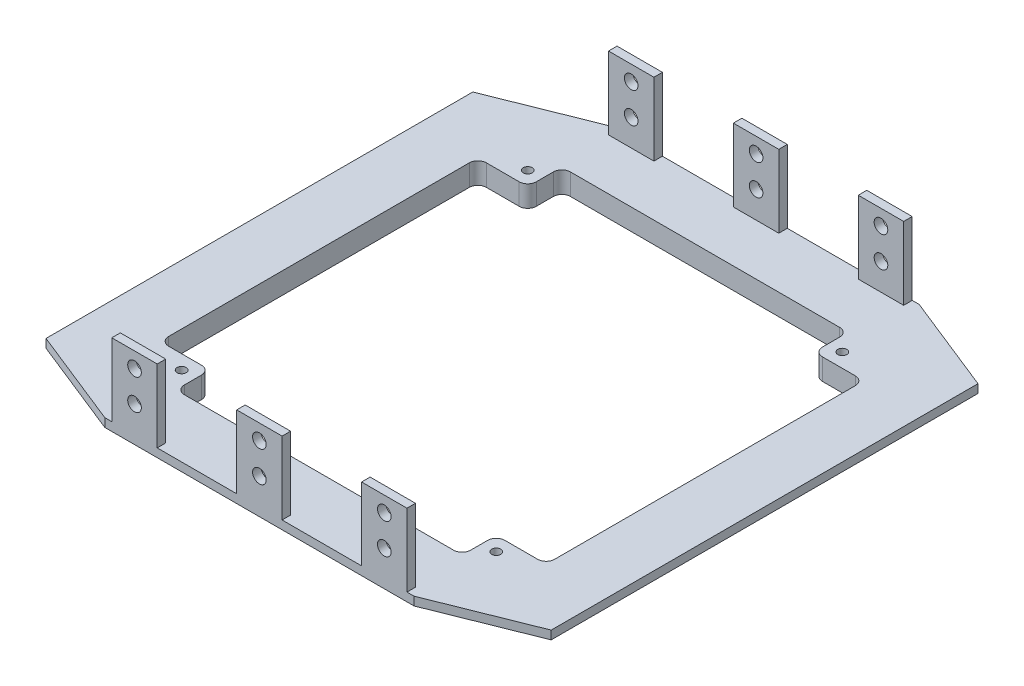
SolidWorks part; units mm, degrees
material "6061-T6 (SS)"
ref_plane "Front Plane" through (0, 0, 0) normal (0, 0, 1) x (1, 0, 0)
ref_plane "Top Plane" through (0, 0, 0) normal (0, 1, 0) x (1, 0, 0)
ref_plane "Right Plane" through (0, 0, 0) normal (1, 0, 0) x (0, 0, -1)
sketch "Sketch1" plane through (0, 0, 0) normal (0, 1, 0) x (1, 0, 0)
  line L5 (-35.5, 0) -> (0, 0) construction
  line L6 (-25.5, -35.5) -> (25.5, -35.5)
  line L10 (-35.5, -31.5) -> (-35.5, 31.5)
  line L11 (-25.5, 35.5) -> (25.5, 35.5)
  line L12 (35.5, -31.5) -> (35.5, 31.5)
  line L13 (0, 0) -> (0, 35.5) construction
  line L14 (25.5, -35.5) -> (35.5, -31.5)
  line L15 (25.5, 35.5) -> (35.5, 31.5)
  line L16 (-25.5, -35.5) -> (-35.5, -31.5)
  line L17 (-25.5, 35.5) -> (-35.5, 31.5)
  point P0 (0, 0)
  point P4 (35.5, -35.5)
  dimension "D3" = 4
  dimension "D2" = 10
  dimension "D4" = 71
extrude "Boss-Extrude1" add sketch "Sketch1" along normal mid plane 4.5
sketch "Sketch2" plane through (0, 2.25, 0) normal (0, 1, 0) x (1, 0, 0)
  line L16 (27.2332, -44.5) -> (44.5, -37.5933)
  line L17 (44.5, -37.5933) -> (44.5, 37.5933)
  line L18 (44.5, 37.5933) -> (27.2332, 44.5)
  line L19 (27.2332, 44.5) -> (-27.2332, 44.5)
  line L20 (-27.2332, 44.5) -> (-44.5, 37.5933)
  line L21 (-44.5, 37.5933) -> (-44.5, -37.5933)
  line L22 (-44.5, -37.5933) -> (-27.2332, -44.5)
  line L23 (-27.2332, -44.5) -> (27.2332, -44.5)
  line L24 (27.2332, -44.5) -> (44.5, -37.5933)
  line L25 (44.5, -37.5933) -> (44.5, 37.5933)
  line L26 (44.5, 37.5933) -> (27.2332, 44.5)
  line L27 (27.2332, 44.5) -> (-27.2332, 44.5)
  line L28 (-27.2332, 44.5) -> (-44.5, 37.5933)
  line L29 (-44.5, 37.5933) -> (-44.5, -37.5933)
  line L30 (-44.5, -37.5933) -> (-27.2332, -44.5)
  line L31 (-27.2332, -44.5) -> (27.2332, -44.5)
  dimension "D1" = 9
extrude "Boss-Extrude2" add sketch "Sketch2" along normal blind 1.5
mirror "Mirror1" about plane through (0, 0, 0) normal (0, 1, 0) of "Boss-Extrude2"
sketch "Sketch3" plane through (0, 0, 0) normal (0, 1, 0) x (1, 0, 0)
  line L16 (-25.2111, -34) -> (25.2111, -34)
  line L17 (25.2111, -34) -> (34, -30.4845)
  line L18 (34, -30.4845) -> (34, 30.4845)
  line L19 (34, 30.4845) -> (25.2111, 34)
  line L20 (25.2111, 34) -> (-25.2111, 34)
  line L21 (-25.2111, 34) -> (-34, 30.4845)
  line L22 (-34, 30.4845) -> (-34, -30.4845)
  line L23 (-34, -30.4845) -> (-25.2111, -34)
  line L24 (-25.2111, -34) -> (25.2111, -34)
  line L25 (25.2111, -34) -> (34, -30.4845)
  line L26 (34, -30.4845) -> (34, 30.4845)
  line L27 (34, 30.4845) -> (25.2111, 34)
  line L28 (25.2111, 34) -> (-25.2111, 34)
  line L29 (-25.2111, 34) -> (-34, 30.4845)
  line L30 (-34, 30.4845) -> (-34, -30.4845)
  line L31 (-34, -30.4845) -> (-25.2111, -34)
  dimension "D1" = 10.5
extrude "Cut-Extrude1" cut sketch "Sketch3" against normal through all both and the other way through all
sketch "Sketch5" plane through (0, 0, 0) normal (0, 0, 1) x (1, 0, 0)
  line L0 (0, 0) -> (0, 16.55) construction
  line L1 (-27.2332, 3.75) -> (27.2332, 3.75) construction
  line L2 (-26, 3.75) -> (-18, 3.75)
  line L3 (-26, 3.75) -> (-26, 16.55)
  line L4 (-26, 16.55) -> (-18, 16.55)
  line L5 (-18, 3.75) -> (-18, 16.55)
  line L6 (-22, 16.55) -> (-22, 3.75) construction
  line L11 (4, 16.55) -> (-4, 16.55)
  line L12 (-4, 16.55) -> (-4, 3.75)
  line L13 (-4, 3.75) -> (4, 3.75)
  line L14 (22, 16.55) -> (22, 3.75) construction
  line L15 (4, 16.55) -> (4, 3.75)
  line L16 (18, 3.75) -> (18, 16.55)
  line L17 (26, 16.55) -> (18, 16.55)
  line L18 (26, 3.75) -> (26, 16.55)
  line L19 (26, 3.75) -> (18, 3.75)
  point P1 (-22, 3.75)
  point P13 (0, 16.9896)
  point P19 (0, 3.75)
  dimension "D1" = 22
  dimension "D3" = 12.8
  dimension "D2" = 8
  dimension "D4" = 8
extrude "Boss-Extrude3" add sketch "Sketch5" against normal blind 1.5 from surface starting at face at (0, 3, 44.5)
extrude "Boss-Extrude4" add sketch "Sketch5<2>" along normal blind 1.5 from surface starting at face at (0, 3, -44.5)
sketch "Sketch5<2>" plane through (0, 0, 0) normal (0, 0, 1) x (1, 0, 0) same geometry as "Sketch5"
sketch "Sketch6" plane through (0, 0, 0) normal (0, 0, 1) x (1, 0, 0)
  line L0 (-22, 16.55) -> (-22, 13.85) construction
  line L1 (-18, 16.55) -> (-26, 16.55) construction
  line L2 (0, 0) -> (0, 13.85) construction
  line L3 (-22, 13.85) -> (-22, 8.45) construction
  line L4 (-22, 13.85) -> (22, 13.85) construction
  line L5 (-22, 8.45) -> (22, 8.45) construction
  line L6 (22, 13.85) -> (22, 8.45) construction
  line L7 (22, 16.55) -> (22, 13.85) construction
  circle A0 centre (-22, 13.85) radius 1.2
  circle A2 centre (-22, 8.45) radius 1.2
  circle A4 centre (0, 13.85) radius 1.2
  circle A5 centre (0, 8.45) radius 1.2
  circle A6 centre (22, 8.45) radius 1.2
  circle A7 centre (22, 13.85) radius 1.2
  point P14 (0, 14.3217)
  dimension "D1" = 2.4
  dimension "D2" = 2.7
  dimension "D3" = 5.4
extrude "Cut-Extrude3" cut sketch "Sketch6" against normal through all both and the other way through all
sketch "Sketch7" plane through (0, 0, 0) normal (0, 1, 0) x (1, 0, 0)
  line L0 (44.5, -37.5933) -> (44.5, 37.5933) construction
  line L1 (-44.5, 44.5) -> (44.5, 44.5)
  line L2 (-44.5, 44.5) -> (-44.5, -44.5)
  line L3 (-44.5, -44.5) -> (44.5, -44.5)
  line L4 (44.5, 44.5) -> (44.5, -44.5)
  line L5 (-44.5, 44.5) -> (44.5, -44.5) construction
  line L6 (-44.5, -44.5) -> (44.5, 44.5) construction
  line L8 (-18, -44.5) -> (-4, -44.5) construction
  point P1 (0, 0)
extrude "Cut-Extrude4" cut sketch "Sketch7" against normal through all
sketch "Sketch8" plane through (0, 0, 0) normal (0, 1, 0) x (1, 0, 0)
  line L0 (-25.2111, -34) -> (-34, -30.4845)
  line L1 (-34, -30.4845) -> (-34, -27.9845)
  line L2 (-34, 30.4845) -> (-34, -30.4845) construction
  line L3 (-34, -27.9845) -> (-25.2111, -27.9845)
  line L4 (-25.2111, -27.9845) -> (-25.2111, -34)
  line L5 (0, 44.5) -> (0, -44.5) construction
  line L7 (-44.5, 0) -> (44.5, 0) construction
  line L8 (44.5, -37.5933) -> (44.5, 37.5933) construction
  line L9 (-34, -30.4845) -> (-25.2111, -30.4845) construction
  line L10 (34, -30.4845) -> (25.2111, -30.4845) construction
  line L11 (25.2111, -27.9845) -> (25.2111, -34)
  line L12 (34, -27.9845) -> (25.2111, -27.9845)
  line L13 (34, -30.4845) -> (34, -27.9845)
  line L14 (25.2111, -34) -> (34, -30.4845)
  line L15 (34, 30.4845) -> (25.2111, 30.4845) construction
  line L16 (-34, 30.4845) -> (-25.2111, 30.4845) construction
  line L17 (25.2111, 34) -> (34, 30.4845)
  line L18 (34, 30.4845) -> (34, 27.9845)
  line L19 (34, 27.9845) -> (25.2111, 27.9845)
  line L20 (25.2111, 27.9845) -> (25.2111, 34)
  line L21 (-25.2111, 27.9845) -> (-25.2111, 34)
  line L22 (-34, 27.9845) -> (-25.2111, 27.9845)
  line L23 (-34, 30.4845) -> (-34, 27.9845)
  line L24 (-25.2111, 34) -> (-34, 30.4845)
  line L25 (-27.2332, -44.5) -> (27.2332, -44.5) construction
  point P4 (-27.7111, -30.4845)
  point P11 (0, 0)
  point P14 (0, 0)
  point P20 (0, 0)
  point P25 (27.7111, -30.4845)
  point P34 (-27.7111, 30.4845)
  point P35 (27.7111, 30.4845)
  dimension "D2" = 2.5
  dimension "D1" = 2.5
extrude "Boss-Extrude5" add sketch "Sketch8" along normal up to surface (3.75 mm away) up to face at (0, 3.75, 0)
fillet "Fillet2" radius 1.5 12 edges at (-34, 1.875, 27.9845) (-25.2111, 1.875, 34) (25.2111, 1.875, 34) (34, 1.875, 27.9845) (25.2111, 1.875, -34) (34, 1.875, -27.9845) (-34, 1.875, -27.9845) (-25.2111, 1.875, -34) (25.2111, 1.875, -27.9845) (-25.2111, 1.875, -27.9845) (-25.2111, 1.875, 27.9845) (25.2111, 1.875, 27.9845)
hole_wizard "M2x0.4 Tapped Hole1" positions "Sketch11" profile "Sketch12" tap size "M2x0.4" standard "ANSI Metric" end condition through all
sketch "Sketch11" plane through (0, 3.75, 0) normal (0, 1, 0) x (1, 0, 0)
  point P0 (-27.7111, 30.4845)
  point P3 (27.7111, 30.4845)
  point P6 (27.7111, -30.4845)
  point P9 (-27.7111, -30.4845)
sketch "Sketch12" plane through (-27.7111, 3.75, -30.4845) normal (1, 0, 0) x (0, 0, 1)
  line L0 (0, 0) -> (0, 3.75)
  line L1 (0, 3.75) -> (0.8, 3.75)
  line L2 (0.8, 3.75) -> (0.8, 0)
  line L5 (0.8, 0) -> (0, 0)
  line L11 (0, -6.35) -> (0, 107.95) construction
  dimension "Thru Tap Drill Dia." = 1.6
  dimension "Thru Tap Drill Depth" = 3.75
cosmetic thread "Hole Thread1" parameters "D2"=2
cosmetic thread "Hole Thread2" parameters "D2"=2
cosmetic thread "Hole Thread3" parameters "D2"=2
cosmetic thread "Hole Thread4" parameters "D2"=2
